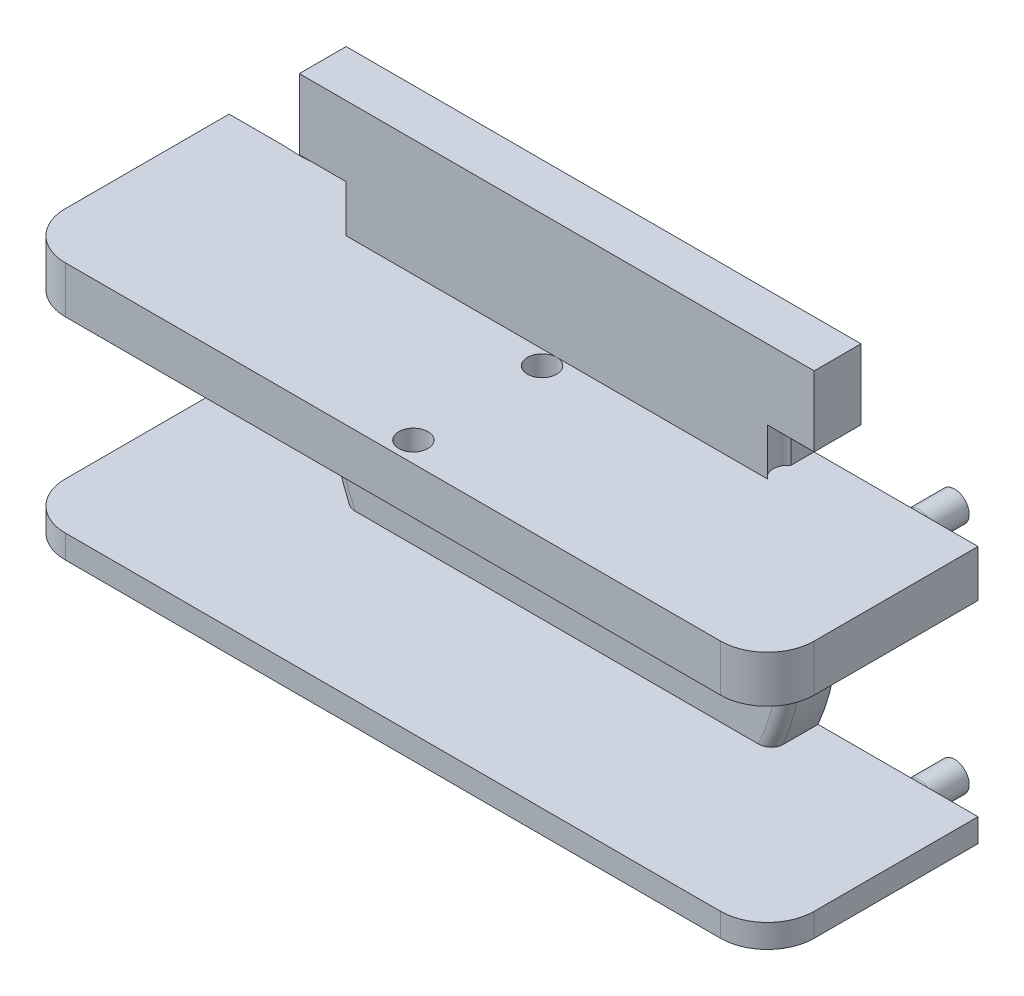
SolidWorks part; units mm, degrees
material "UNOBTANIUM"
ref_plane "Top Plane" through (0, 0, 0) normal (0, 0, 1) x (1, 0, 0)
ref_plane "Right Plane" through (0, 0, 0) normal (0, 1, 0) x (1, 0, 0)
ref_plane "Front Plane" through (0, 0, 0) normal (1, 0, 0) x (0, 0, -1)
ref_axis "x-axis" through (-17.6, 0, 0) along (1, 0, 0)
ref_axis "y-axis" through (0, -9.7375, 0) along (0, 1, 0)
ref_axis "z-axis" through (0, 0, 8.775) along (0, 0, -1)
sketch "Sketch1" plane through (0, 0, 0) normal (0, 0, 1) x (1, 0, 0)
  line L0 (-11, 6) -> (-11, 11)
  line L1 (-11, -6) -> (11, -6)
  line L2 (-11, -6) -> (-11, 6)
  line L3 (-11, 6) -> (11, 6) construction
  line L4 (11, -6) -> (11, 6)
  line L5 (-11, -6) -> (11, 6) construction
  line L6 (-11, 6) -> (11, -6) construction
  line L7 (-11, 11) -> (11, 11)
  line L8 (11, 11) -> (11, 6)
  circle A0 centre (0, 0) radius 9.25 construction
  point P0 (0, 0)
  dimension "D1" = 18.5
  dimension "D2" = 22
  dimension "D3" = 12
  dimension "D4" = 5
extrude "Boss-Extrude1" add sketch "Sketch1" along normal blind 2
sketch "Sketch2" plane through (0, 0, 2) normal (0, 0, -1) x (-1, 0, 0)
  circle A0 centre (0, 0) radius 1.51
  dimension "D1" = 3.02
extrude "Boss-Extrude2" add sketch "Sketch2" along normal blind 4 separate body
sketch "Sketch3" plane through (0, 0, 0) normal (0, 0, -1) x (-1, 0, 0)
  line L0 (11, -6) -> (-11, 6) construction
  circle A0 centre (0, 0) radius 3.5
  dimension "D1" = 7
extrude "Boss-Extrude3" add sketch "Sketch3" along normal blind 1
sketch "Sketch4" plane through (0, 0, 0) normal (0, 0, -1) x (-1, 0, 0)
  line L0 (11, -6) -> (-11, -6) construction
  line L1 (11, 11) -> (9, 11)
  line L2 (11, 11) -> (11, -6)
  line L3 (11, -6) -> (9, -6)
  line L4 (9, 11) -> (9, -6)
  line L5 (0, -6) -> (0, 11) construction
  line L7 (-9, 11) -> (-9, -6)
  line L8 (-11, -6) -> (-9, -6)
  line L9 (-11, 11) -> (-11, -6)
  line L10 (-11, 11) -> (-9, 11)
  line L11 (11, 11) -> (-11, 11) construction
  dimension "D1" = 2
extrude "Boss-Extrude4" add sketch "Sketch4" along normal blind 0.001
sketch "Sketch5" plane through (0, 0, 0) normal (0, 0, -1) x (-1, 0, 0)
  line L0 (-9, -6) -> (-9, 11) construction
  line L1 (9, 11) -> (-9, 11)
  line L2 (9, 11) -> (9, 9)
  line L3 (9, 9) -> (-9, 9)
  line L4 (-9, 11) -> (-9, 9)
  dimension "D1" = 2
extrude "Boss-Extrude5" add sketch "Sketch5" along normal up to surface (0.001 mm away) up to face at (-10, 2.5, -0.001)
sketch "Sketch6" plane through (11, 0, 0) normal (1, 0, 0) x (0, 0, -1)
  line L0 (-2, -6) -> (-2, 11) construction
  line L1 (0.001, -6) -> (-2, -6)
  line L2 (0.001, -6) -> (0.001, -4)
  line L3 (0.001, -4) -> (-2, -4)
  line L4 (-2, -6) -> (-2, -4)
  line L6 (0.001, 11) -> (0.001, -6) construction
  line L7 (-2, 6) -> (0.001, 6)
  line L8 (-2, 6) -> (-2, 4)
  line L9 (-2, 4) -> (0.001, 4)
  line L10 (0.001, 6) -> (0.001, 4)
  point P8 (0, 0)
  dimension "D1" = 2
extrude "Boss-Extrude6" add sketch "Sketch6" along normal blind 5
mirror "Mirror1" about plane through (0, 0, 0) normal (1, 0, 0) of "Boss-Extrude6"
sketch "Sketch7" plane through (0, 0, -0.001) normal (0, 0, -1) x (-1, 0, 0)
  line L0 (-9, -6) -> (-9, 9) construction
  line L1 (-9, 0) -> (-9, 9)
  line L2 (-9, 9) -> (0, 9)
  line L3 (-9, 0) -> (-9, -6)
  line L4 (-9, -6) -> (-6.7082, -6)
  line L5 (11, -6) -> (-11, -6) construction
  arc A0 (0, 9) -> (-6.7082, -6) centre (0, 0) ccw
  line M18 (-9, -6) -> (-9, 9)
  line M19 (-9, 9) -> (9, 9)
extrude "Boss-Extrude7" add sketch "Sketch7" against normal up to surface (0.001 mm away) contours A0 L4 M18 | A0 M19 M18 region at (8.3306, -4.5409, -0.001) region at (6.9897, 6.9897, -0.001) up to face at (3.5, 0, 0)
sketch "Sketch8" plane through (0, 0, -0.001) normal (0, 0, -1) x (-1, 0, 0)
  line L0 (-11, 4) -> (-9.1652, 4)
  line L1 (-11, 4) -> (-11, -4)
  line L2 (-11, -4) -> (-9.1652, -4)
  arc A1 (-9.1652, 4) -> (-9.1652, -4) centre (0, 0) ccw
  dimension "D1" = 10
extrude "Cut-Extrude1" cut sketch "Sketch8" against normal through all
sketch "Sketch9" plane through (0, 0, -0.001) normal (0, 0, -1) x (-1, 0, 0)
  line L0 (-16, -4) -> (-9.1652, -4) construction
  line L1 (-8.0623, 4) -> (-11, 4)
  line L2 (-8.0623, 4) -> (-8.0623, -4)
  line L3 (-8.0623, -4) -> (-11, -4)
  line L4 (-11, 4) -> (-11, -4)
  line L5 (-11, -6) -> (-11, 6) construction
  arc A0 (0, 9) -> (-6.7082, -6) centre (0, 0) ccw construction
  arc A1 (0, 9) -> (-6.7082, -6) centre (0, 0) ccw construction
extrude "Cut-Extrude2" cut sketch "Sketch9" against normal up to surface (0.001 mm away) up to face at (3.5, 0, 0)
mirror "Mirror2" about plane through (0, 0, 0) normal (1, 0, 0) of "Cut-Extrude2", "Boss-Extrude7", "Cut-Extrude1"
sketch "Sketch21" plane through (0, 0, -0.001) normal (0, 0, -1) x (-1, 0, 0)
  circle A0 centre (0, 0) radius 9.75
  circle A1 centre (0, 0) radius 9 construction
  circle A2 centre (0, 0) radius 3.5 construction
  circle A3 centre (0, 0) radius 3.5
  dimension "D1" = 0.75
extrude "Cut-Extrude11" cut sketch "Sketch21" against normal up to surface (0.001 mm away) up to face at (0, -0.7091, 0)
sketch "Sketch10" plane through (0, 0, 2) normal (0, 0, 1) x (1, 0, 0)
  line L0 (-16, -4) -> (-16, -6) construction
  line L1 (16, -6) -> (-16, -6)
  line L2 (16, -6) -> (16, -4)
  line L3 (16, -4) -> (-16, -4)
  line L4 (-16, -6) -> (-16, -4)
  line L5 (-16, -4) -> (-9.1652, -4) construction
  line L7 (-16, 6) -> (16, 6)
  line L8 (-16, 6) -> (-16, 4)
  line L9 (-16, 4) -> (16, 4)
  line L10 (16, 6) -> (16, 4)
  point P13 (0, 0)
extrude "Boss-Extrude8" add sketch "Sketch10" along normal blind 7
fillet "Fillet1" radius 0.5 2 edges at (10, 0, 2) (-10, 0, 2)
sketch "Sketch11" plane through (0, 0, -0.001) normal (0, 0, -1) x (-1, 0, 0)
  line L0 (-16, -5) -> (-13, -5) construction
  line L1 (-16, -6) -> (-16, -4) construction
  circle A0 centre (-13, -5) radius 0.625
  dimension "D1" = 1.25
  dimension "D2" = 3
extrude "Boss-Extrude9" add sketch "Sketch11" along normal blind 2
sketch "Sketch14" plane through (0, 0, -0.001) normal (0, 0, -1) x (-1, 0, 0)
  line L1 (11, 6) -> (9, 6)
  line L2 (11, 6) -> (11, 8)
  line L3 (11, 8) -> (9, 8)
  line L4 (9, 6) -> (9, 8)
  line L5 (-11, 6) -> (-9, 6)
  line L6 (-11, 6) -> (-11, 8)
  line L7 (-11, 8) -> (-9, 8)
  line L8 (-9, 6) -> (-9, 8)
  dimension "D1" = 18
  dimension "D2" = 2
extrude "Cut-Extrude5" cut sketch "Sketch14" against normal through all
sketch "Sketch12" plane through (0, 0, -0.001) normal (0, 0, -1) x (-1, 0, 0)
  line L0 (-16, -5) -> (-13, -5) construction
  line L1 (-16, -6) -> (-16, -4) construction
  line L3 (16, -5) -> (13, -5) construction
  line L4 (16, -6) -> (16, -4) construction
  circle A0 centre (13, -5) radius 0.675
  circle A1 centre (-13, -5) radius 0.625 construction
  circle A2 centre (-13, -5) radius 0.625 construction
  dimension "D1" = 1.35
  dimension "D2" = 1.25
extrude "Cut-Extrude3" cut sketch "Sketch12" against normal blind 2.5
sketch "Sketch16" plane through (0, 6, 0) normal (0, 1, 0) x (1, 0, 0)
  line L0 (-9, -2) -> (-9, 0.001) construction
  line L1 (-9, -1) -> (-9, -2)
  arc A1 (-9, -1) -> (-9, -2) centre (-9.375, -1.5) cw
  dimension "D1" = 0.25
  dimension "D2" = 1
extrude "Cut-Extrude6" cut sketch "Sketch16" along normal blind 2
mirror "Mirror3" about plane through (0, 0, 0) normal (0, 1, 0) of "Boss-Extrude9", "Cut-Extrude3"
mirror "Mirror4" about plane through (0, 0, 0) normal (1, 0, 0) of "Cut-Extrude6"
fillet "Fillet2" radius 0.5 2 edges at (12.375, 5, -0.001) (13.625, -5, -0.001)
fillet "Fillet3" radius 0.5 2 edges at (-13.675, 5, -0.001) (-13.675, -5, -0.001)
fillet "Fillet4" radius 2 4 edges at (16, -5, 9) (16, 5, 9) (-16, -5, 9) (-16, 5, 9)
sketch "Sketch17" plane through (0, -6, 0) normal (0, -1, 0) x (1, 0, 0)
  line L0 (-16, 7) -> (-16, -0.001) construction
  line L1 (-14, 9) -> (14, 9) construction
  line L2 (16, 7) -> (16, -0.001) construction
  line L3 (-16, 7) -> (-16, -0.001)
  line L4 (-14, 9) -> (14, 9)
  line L5 (16, 7) -> (16, -0.001)
  line L6 (14.5, 7) -> (14.5, -0.001)
  line L8 (-14, 7.5) -> (14, 7.5)
  line L9 (-14.5, 7) -> (-14.5, -0.001)
  line L10 (14.5, -0.001) -> (16, -0.001)
  line L11 (-14.5, -0.001) -> (-16, -0.001)
  arc A0 (-14, 9) -> (-16, 7) centre (-14, 7) ccw construction
  arc A1 (16, 7) -> (14, 9) centre (14, 7) ccw construction
  arc A2 (-14, 9) -> (-16, 7) centre (-14, 7) ccw
  arc A3 (16, 7) -> (14, 9) centre (14, 7) ccw
  arc A4 (14.5, 7) -> (14, 7.5) centre (14, 7) ccw
  arc A5 (-14, 7.5) -> (-14.5, 7) centre (-14, 7) ccw
  dimension "D1" = 1.5
extrude "Cut-Extrude7" cut sketch "Sketch17" against normal blind 1 and the other way through all
sketch "Sketch19" plane through (0, 6, 0) normal (0, 1, 0) x (1, 0, 0)
  line L0 (9, -2) -> (-9, -2) construction
  line L1 (0, -2.625) -> (0, -2) construction
  line L2 (9, -2) -> (-9, -2) construction
  circle A0 centre (0, -2.625) radius 0.625
  circle A1 centre (0, -8.125) radius 0.625
  point P4 (0, -2)
  dimension "D1" = 1.25
  dimension "D2" = 5.5
extrude "Cut-Extrude9" cut sketch "Sketch19" against normal up to surface (2 mm away) up to face at (0.0154, 4, 1.9997)
sketch "Sketch20" plane through (0, 0, -0.001) normal (0, 0, -1) x (-1, 0, 0)
  line L0 (-9, 8) -> (-11, 8) construction
  line L1 (-11, 11) -> (-9, 11)
  line L2 (-11, 11) -> (-11, 8)
  line L3 (-11, 8) -> (-9, 8)
  line L4 (-9, 11) -> (-9, 8)
  line L5 (11, 11) -> (-11, 11) construction
  line L6 (11, 8) -> (9, 8)
  line L7 (11, 8) -> (11, 11)
  line L8 (11, 11) -> (9, 11)
  line L9 (9, 8) -> (9, 11)
  dimension "D1" = 2
combine bodies "Combine2" operation type subtract main body 122 bodies to subtract 102
equation "\"D1@Sketch12\"=\"D2@Sketch12\"+.1"
